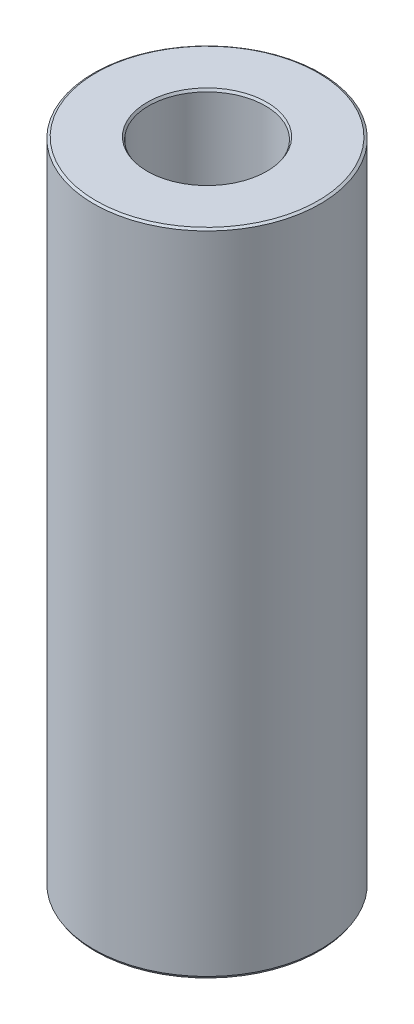
SolidWorks part; units mm, degrees
ref_plane "Front Plane" through (0, 0, 0) normal (0, 0, 1) x (1, 0, 0)
ref_plane "Top Plane" through (0, 0, 0) normal (0, 1, 0) x (1, 0, 0)
ref_plane "Right Plane" through (0, 0, 0) normal (1, 0, 0) x (0, 0, -1)
sketch "Sketch1" plane through (0, 0, 0) normal (0, 1, 0) x (1, 0, 0)
  circle A0 centre (0, 0) radius 55
  dimension "SLEEVE_OD" = 110
extrude "Boss-Extrude1" add sketch "Sketch1" along normal blind 315.1694
sketch "Sketch2" plane through (0, 0, 0) normal (0, 1, 0) x (1, 0, 0)
  circle A0 centre (0, 0) radius 28.3115
  dimension "BORE_D" = 56.623
extrude "Cut-Extrude1" cut sketch "Sketch2" along normal through all
chamfer "Chamfer1" distance 0.7264 angle 57.851 4 edges at (0, 315.1694, 28.3115) (0, 0, 28.3115) (0, 0, 55) (0, 315.1694, 55) first distance on face at (0, 315.1694, 28.3115) first distance on face at (0, 0, 28.3115) first distance on face at (0, 315.1694, 55)
